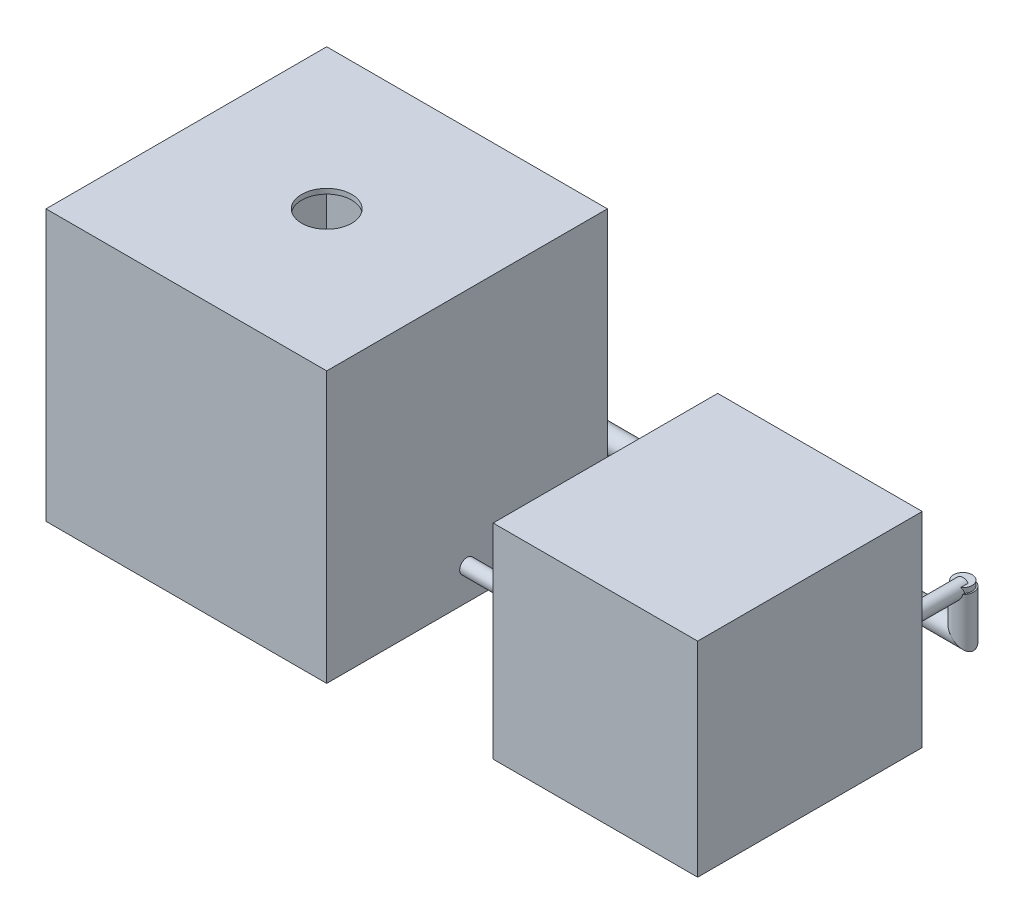
SolidWorks part; units mm, degrees
ref_plane "Front Plane" through (0, 0, 0) normal (0, 0, 1) x (1, 0, 0)
ref_plane "Top Plane" through (0, 0, 0) normal (0, 1, 0) x (1, 0, 0)
ref_plane "Right Plane" through (0, 0, 0) normal (1, 0, 0) x (0, 0, -1)
sketch "Sketch1" plane through (0, 0, 0) normal (0, 1, 0) x (1, 0, 0)
  line L1 (-140, 140) -> (140, 140)
  line L2 (-140, 140) -> (-140, -140)
  line L3 (-140, -140) -> (140, -140)
  line L4 (140, 140) -> (140, -140)
  line L5 (-140, 140) -> (140, -140) construction
  line L6 (-140, -140) -> (140, 140) construction
  line L7 (138, 138) -> (-138, 138)
  line L8 (138, 138) -> (138, -138)
  line L9 (138, -138) -> (-138, -138)
  line L10 (-138, 138) -> (-138, -138)
  line L11 (138, 138) -> (-138, -138) construction
  line L12 (138, -138) -> (-138, 138) construction
  point P0 (0, 0)
  point P6 (0, 0)
  dimension "D1" = 280
  dimension "D2" = 280
  dimension "D3" = 2
  dimension "D4" = 2
extrude "Boss-Extrude1" add sketch "Sketch1" along normal blind 260
sketch "Sketch2" plane through (0, 260, 0) normal (0, 1, 0) x (1, 0, 0)
  line L1 (-140, -140) -> (140, -140)
  line L2 (-140, -140) -> (-140, 140)
  line L3 (-140, 140) -> (140, 140)
  line L4 (140, -140) -> (140, 140)
extrude "Boss-Extrude5" add sketch "Sketch2" along normal blind 5
sketch "Sketch3" plane through (0, 0, 0) normal (0, -1, 0) x (-1, 0, 0)
  line L0 (-140, -140) -> (-140, 140) construction
  line L1 (140, 140) -> (-140, 140)
  line L2 (140, 140) -> (140, -140)
  line L3 (140, -140) -> (-140, -140)
  line L4 (-140, 140) -> (-140, -140)
  line L5 (140, -140) -> (-140, -140) construction
extrude "Boss-Extrude6" add sketch "Sketch3" along normal blind 5
sketch "Sketch4" plane through (0, 265, 0) normal (0, 1, 0) x (1, 0, 0)
  circle A0 centre (0, 0) radius 25
extrude "Cut-Extrude1" cut sketch "Sketch4" against normal blind 5
sketch "Sketch5" plane through (-140, 0, 0) normal (-1, 0, 0) x (0, 0, 1)
  circle A0 centre (0, 26.5768) radius 6.35
extrude "Cut-Extrude2" cut sketch "Sketch5" against normal blind 412
sketch "Sketch6" plane through (-140, 0, 0) normal (-1, 0, 0) x (0, 0, 1)
  circle A0 centre (0, 26.5768) radius 6.35
sketch "Sketch7" plane through (140, 0, 0) normal (1, 0, 0) x (0, 0, -1)
  circle A0 centre (0, 26.5768) radius 6.35
extrude "Extrude-Thin2" add sketch "Sketch7" along normal blind 140 thin
sketch "Sketch8" plane through (280, 0, 0) normal (1, 0, 0) x (0, 0, -1)
  line L1 (110, -13.4232) -> (-110, -13.4232)
  line L2 (110, -13.4232) -> (110, 186.5768)
  line L3 (110, 186.5768) -> (-110, 186.5768)
  line L4 (-110, -13.4232) -> (-110, 186.5768)
  circle A0 centre (0, 26.5768) radius 6.35 construction
  dimension "D1" = 200
  dimension "D2" = 40
  dimension "D3" = 110
  dimension "D4" = 220
extrude "Extrude-Thin3" add sketch "Sketch8" along normal blind 200 separate body thin thin type one direction wall 2
sketch "Sketch9" plane through (480, 0, 0) normal (1, 0, 0) x (0, 0, -1)
  line L0 (112, -15.4232) -> (112, 188.5768) construction
  line L1 (-112, 188.5768) -> (112, 188.5768)
  line L2 (-112, 188.5768) -> (-112, -15.4232)
  line L3 (-112, -15.4232) -> (112, -15.4232)
  line L4 (112, 188.5768) -> (112, -15.4232)
  line L5 (-112, -15.4232) -> (112, -15.4232) construction
extrude "Boss-Extrude7" add sketch "Sketch9" along normal blind 2
sketch "Sketch11" plane through (280, 0, 0) normal (-1, 0, 0) x (0, 0, 1)
  line L0 (112, -15.4232) -> (-112, -15.4232) construction
  line L1 (112, 188.5768) -> (-112, 188.5768)
  line L2 (112, 188.5768) -> (112, -15.4232)
  line L3 (112, -15.4232) -> (-112, -15.4232)
  line L4 (-112, 188.5768) -> (-112, -15.4232)
extrude "Boss-Extrude8" add sketch "Sketch11" along normal blind 2
sketch "Sketch12" plane through (0, 0, -112) normal (0, 0, -1) x (-1, 0, 0)
  line L0 (-482, -15.4232) -> (-278, -15.4232) construction
  circle A0 centre (-382.5597, 4.5768) radius 6.35
  dimension "D1" = 20
extrude "Extrude-Thin4" add sketch "Sketch12" along normal blind 140 thin
sketch3d "3DSketch2"
  line L0 (382.5597, 4.5768, -252) -> (382.5597, -35.4232, -252)
  line L1 (382.5597, 4.5768, -252) -> (382.5597, 4.5768, -112) construction
  line L2 (382.5597, 4.5768, -252) -> (382.5597, 4.5768, -112) construction
  line L3 (382.5597, -35.4232, -252) -> (222.5597, -35.4232, -252)
  point P7 (0, 0, 0)
  dimension "D1" = 40
  dimension "D2" = 160
other "Structural Member1"
ref_plane "Plane1" through (382.5597, 4.5768, -252) normal (0, -1, 0) x (1, 0, 0)
sketch "Sketch14" plane through (382.5597, 4.5768, -252) normal (0, -1, 0) x (1, 0, 0)
  circle A0 centre (0, 0) radius 7.8994
  circle A1 centre (0, 0) radius 10.668
  circle A2 centre (0, 0) radius 6.35 construction
  point P5 (0, 0)
  dimension "In_dia" = 15.7988
  dimension "Out_dia" = 21.336
  dimension "D1" = 12.7
other "End cap1" parameters "D1"=5, "D2"=3, "D3"=3, "D4"=0
sketch3d "3DSketch6"
  line L0 (0, 32.2754, -140) -> (0, 32.2754, -255)
  line L1 (0, 32.2754, -255) -> (0, -47.7246, -255)
  line L2 (0, -47.7246, -255) -> (100, -47.7246, -255)
  dimension "D1" = 115
  dimension "D2" = 0
  dimension "D3" = 100
  dimension "D4" = 80
other "Structural Member2"
ref_plane "Plane2" through (0, 32.2754, -140) normal (0, 0, -1) x (1, 0, 0)
sketch "Sketch15" plane through (0, 32.2754, -140) normal (0, 0, -1) x (1, 0, 0)
  circle A0 centre (0, 0) radius 7.8994
  circle A1 centre (0, 0) radius 10.668
  circle A2 centre (0, 0) radius 6.35 construction
  point P5 (0, 0)
  dimension "In_dia" = 15.7988
  dimension "Out_dia" = 21.336
  dimension "D1" = 12.7
sketch "Sketch16" plane through (-140, 0, 0) normal (-1, 0, 0) x (0, 0, 1)
  circle A0 centre (0, 26.5768) radius 6.25
extrude "Boss-Extrude9" add sketch "Sketch16" along normal blind 0.001 and the other way blind 2 separate body
